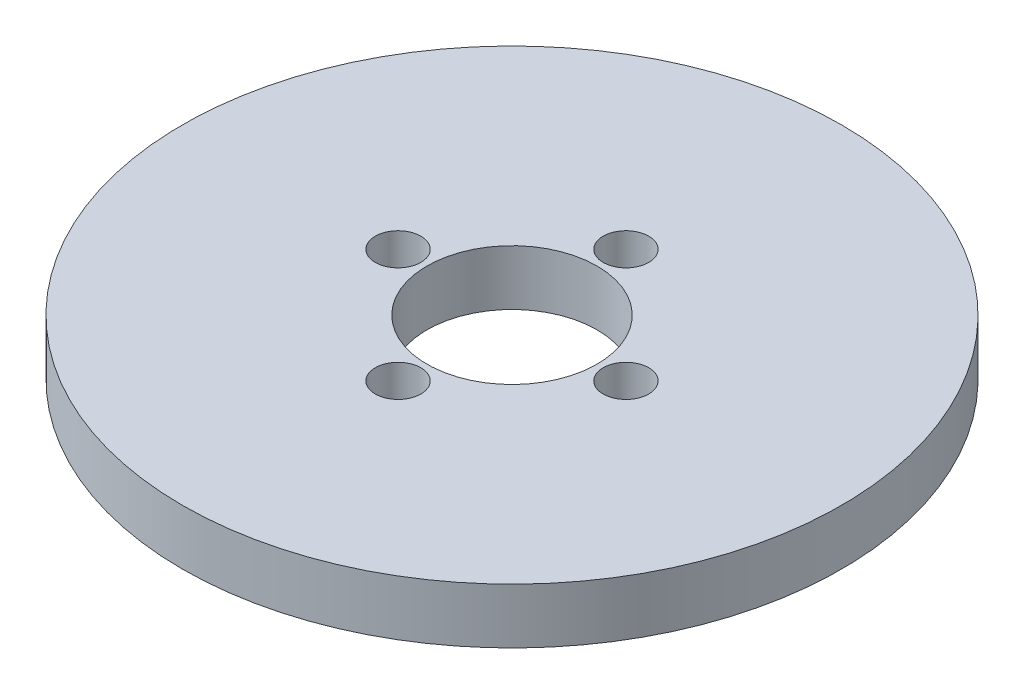
SolidWorks part; units mm, degrees
ref_plane "Front Plane" through (0, 0, 0) normal (0, 0, 1) x (1, 0, 0)
ref_plane "Top Plane" through (0, 0, 0) normal (0, 1, 0) x (1, 0, 0)
ref_plane "Right Plane" through (0, 0, 0) normal (1, 0, 0) x (0, 0, -1)
sketch "Sketch1" plane through (0, 0, 0) normal (0, 1, 0) x (1, 0, 0)
  circle A0 centre (0, 0) radius 77.5
  dimension "FLANGE_OD" = 155
extrude "Boss-Extrude1" add sketch "Sketch1" along normal blind 13
sketch "Sketch2" plane through (0, 0, 0) normal (0, 1, 0) x (1, 0, 0)
  circle A0 centre (0, 0) radius 20
  dimension "BORE_D" = 40
extrude "Cut-Extrude1" cut sketch "Sketch2" along normal through all
sketch "Sketch3" plane through (0, 13, 0) normal (0, 1, 0) x (1, 0, 0)
  circle A0 centre (0, 0) radius 26.7972 construction
  circle A1 centre (-26.7972, 0) radius 5.3575
  dimension "BOLT_D" = 10.7151
  dimension "BOLT_PCD" = 53.5944
extrude "Cut-Extrude2" cut sketch "Sketch3" against normal blind 8.9701
pattern_circular "CirPattern1" count 4 over 360 about axis through (0, 0, 0) along (0, 1, 0) of "Cut-Extrude2"
